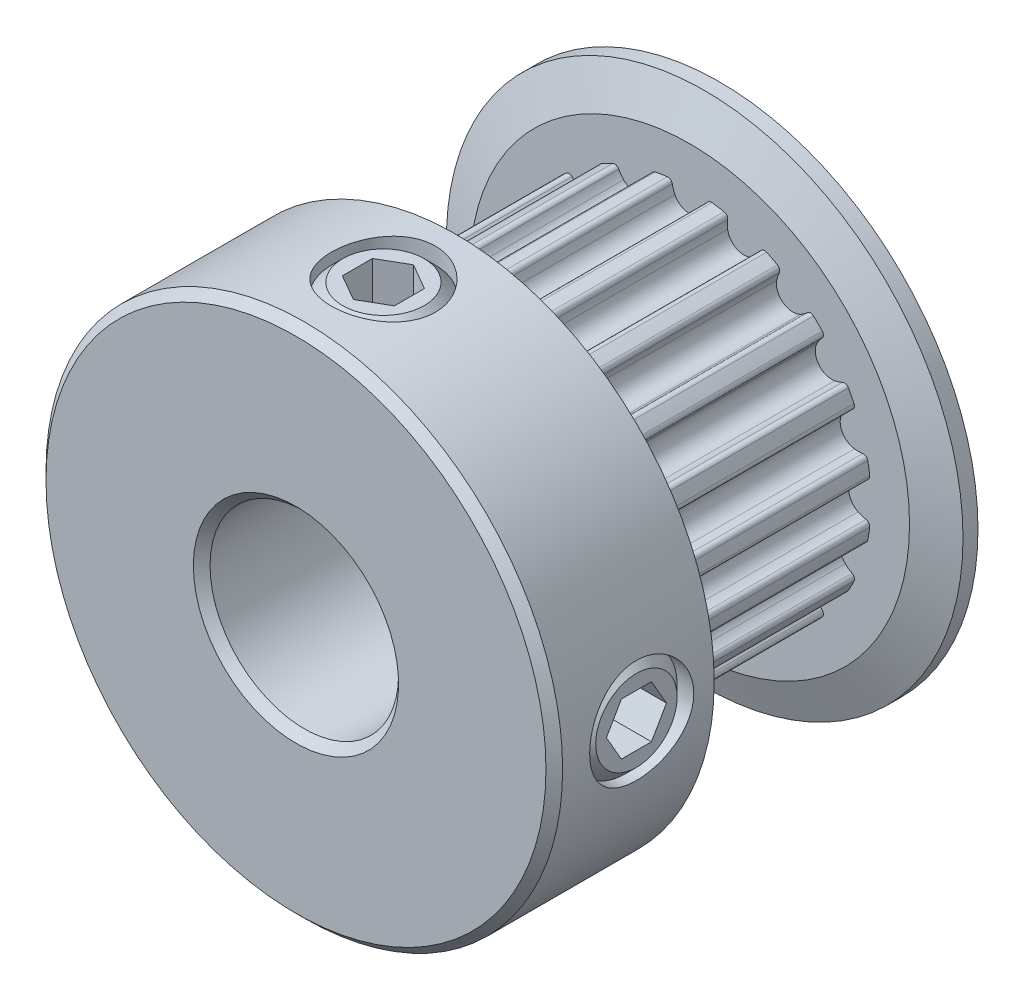
SolidWorks part; units mm, degrees
ref_plane "Front Plane" through (0, 0, 0) normal (0, 0, 1) x (1, 0, 0)
ref_plane "Top Plane" through (0, 0, 0) normal (0, 1, 0) x (1, 0, 0)
ref_plane "Right Plane" through (0, 0, 0) normal (1, 0, 0) x (0, 0, -1)
sketch "Sketch1" plane through (0, 0, 0) normal (0, 0, 1) x (1, 0, 0)
  line L1 (-1.7499, 5.3585) -> (1.7499, 5.3585) construction
  line L4 (0, 0) -> (0, 5.3585) construction
  line L5 (0, 5.3585) -> (0, 11.1847) construction
  line L6 (0, 6.3625) -> (1.9751, 6.0482) construction
  line L7 (1.9751, 6.0482) -> (2.6648, 5.8229) construction
  line L8 (1.9751, 6.0482) -> (1.7499, 5.3585) construction
  line L9 (-1.9751, 6.0482) -> (-1.7499, 5.3585) construction
  line L10 (-1.8963, 5.8067) -> (-2.841, 8.6995)
  line L11 (-2.841, 8.6995) -> (2.841, 8.6995)
  line L12 (2.841, 8.6995) -> (1.8963, 5.8067)
  circle A0 centre (0, 0) radius 6.3625 construction
  circle A1 centre (0, 0) radius 8.6995 construction
  circle A2 centre (0, 0) radius 6.1085 construction
  arc A3 (-0.4989, 5.6703) -> (0.4989, 5.6703) centre (0, 5.9135) ccw
  arc A4 (-0.4989, 5.6703) -> (-0.5855, 5.9387) centre (0.4, 6.1085) cw
  arc A5 (-1.8963, 5.8067) -> (-0.7518, 6.0621) centre (0, 0) cw
  arc A6 (-0.5855, 5.9387) -> (-0.7518, 6.0621) centre (-0.7333, 5.9132) ccw
  arc A7 (1.8963, 5.8067) -> (0.7518, 6.0621) centre (0, 0) ccw
  arc A8 (0.5855, 5.9387) -> (0.7518, 6.0621) centre (0.7333, 5.9132) cw
  arc A9 (0.4989, 5.6703) -> (0.5855, 5.9387) centre (-0.4, 6.1085) ccw
  point P6 (0, 20.9083)
  point P11 (0, 6.3625)
  point P13 (0, 8.6995)
  point P14 (0, 6.1085)
  dimension "D1" = 9.7237
  dimension "D2" = 4.8222
sketch "Sketch2" plane through (0, 0, 0) normal (1, 0, 0) x (0, 0, -1)
  line L0 (-7.135, 3.175) -> (7.135, 3.175)
  line L1 (-7.135, 3.175) -> (-7.135, 8.6995)
  line L2 (-1.75, 8.6995) -> (-7.135, 8.6995)
  line L3 (-2.255, 3.175) -> (-2.255, 8.6995) construction
  line L4 (-2.255, 8.6995) -> (-1.245, 8.6995) construction
  line L5 (-1.245, 8.6995) -> (-1.245, 6.1085) construction
  line L6 (-1.245, 6.1085) -> (6.125, 6.1085)
  line L7 (6.125, 6.1085) -> (6.125, 8.6995) construction
  line L8 (6.125, 8.6995) -> (7.135, 8.6995) construction
  line L9 (7.135, 8.6995) -> (7.135, 3.175)
  line L10 (-7.135, 0) -> (7.135, 0) construction
  line L11 (6.63, 8.6995) -> (6.125, 7.404)
  line L12 (-1.245, 7.404) -> (-1.75, 8.6995)
  line L14 (-1.245, 7.404) -> (-1.245, 6.1085)
  line L15 (6.125, 6.1085) -> (6.125, 7.404)
  line L16 (6.63, 8.6995) -> (7.135, 8.6995)
  arc A0 (-1.245, 7.404) -> (-1.75, 8.6995) centre (-3.1592, 7.404) ccw construction
  arc A1 (6.125, 7.404) -> (6.63, 8.6995) centre (8.0392, 7.404) cw construction
  point P12 (-1.245, 7.404)
  point P14 (-1.75, 8.6995)
  point P20 (6.125, 7.404)
  point P21 (6.63, 8.6995)
  point P25 (6.125, 0)
  point P26 (-1.245, 0)
  dimension "OA" = 14.27
  dimension "Bore" = 6.35
  dimension "Outside Width" = 8.38
  dimension "Inside Width" = 7.37
revolve "Revolve1" add sketch "Sketch2" angle 360 mid plane about L10
sketch "Sketch3" plane through (0, 0, 0) normal (0, 0, 1) x (1, 0, 0)
  line L6 (2.841, 8.6995) -> (-2.841, 8.6995)
  line L7 (1.8963, 5.8067) -> (2.841, 8.6995)
  line L8 (-2.841, 8.6995) -> (-1.8963, 5.8067)
  line L9 (2.841, 8.6995) -> (-2.841, 8.6995)
  line L10 (1.8963, 5.8067) -> (2.841, 8.6995)
  line L11 (-2.841, 8.6995) -> (-1.8963, 5.8067)
  arc A8 (1.8963, 5.8067) -> (0.7518, 6.0621) centre (0, 0) ccw
  arc A9 (0.7518, 6.0621) -> (0.5855, 5.9387) centre (0.7333, 5.9132) ccw
  arc A10 (0.4989, 5.6703) -> (0.5855, 5.9387) centre (-0.4, 6.1085) ccw
  arc A11 (-0.4989, 5.6703) -> (0.4989, 5.6703) centre (0, 5.9135) ccw
  arc A12 (-0.5855, 5.9387) -> (-0.4989, 5.6703) centre (0.4, 6.1085) ccw
  arc A13 (-0.5855, 5.9387) -> (-0.7518, 6.0621) centre (-0.7333, 5.9132) ccw
  arc A14 (-0.7518, 6.0621) -> (-1.8963, 5.8067) centre (0, 0) ccw
  arc A15 (1.8963, 5.8067) -> (0.7518, 6.0621) centre (0, 0) ccw
  arc A16 (0.7518, 6.0621) -> (0.5855, 5.9387) centre (0.7333, 5.9132) ccw
  arc A17 (0.4989, 5.6703) -> (0.5855, 5.9387) centre (-0.4, 6.1085) ccw
  arc A18 (-0.4989, 5.6703) -> (0.4989, 5.6703) centre (0, 5.9135) ccw
  arc A19 (-0.5855, 5.9387) -> (-0.4989, 5.6703) centre (0.4, 6.1085) ccw
  arc A20 (-0.5855, 5.9387) -> (-0.7518, 6.0621) centre (-0.7333, 5.9132) ccw
  arc A21 (-0.7518, 6.0621) -> (-1.8963, 5.8067) centre (0, 0) ccw
  dimension "D1" = 0
extrude "Cut-Extrude1" cut sketch "Sketch3" against normal up to vertex (6.125 mm away) from vertex up to point (0, 6.1085, -6.125) starting at point (0, 6.1085, 1.245)
pattern_circular "CirPattern1" count 20 over 360 about axis through (0, 0, 7.135) along (0, 0, 1) of "Cut-Extrude1"
sketch "Sketch4" plane through (0, 0, 0) normal (1, 0, 0) x (0, -1, 0)
  line L0 (0, -1.245) -> (0, -7.135) construction
  line L1 (-3.175, -7.135) -> (3.175, -7.135) construction
  line L2 (7.404, -1.245) -> (-7.404, -1.245) construction
  circle A0 centre (0, -4.19) radius 1.7526
extrude "Cut-Extrude2" cut sketch "Sketch4" along normal through all
ref_plane "Plane1" through (0, 0, 4.19) normal (0, 0, 1) x (1, 0, 0)
sketch "Sketch5" plane through (0, 0, 4.19) normal (0, 0, 1) x (1, 0, 0)
  line L0 (0, 0) -> (0, 8.6995) construction
  line L1 (3.175, -1.3716) -> (3.175, 0)
  line L2 (3.556, -1.7526) -> (8.1401, -1.7526)
  line L3 (3.175, 0) -> (8.6995, 0) construction
  line L4 (3.175, 0) -> (8.5211, 0)
  line L5 (8.5211, 0) -> (8.5211, -1.3716)
  line L6 (3.556, -1.7526) -> (3.175, -1.3716)
  line L7 (8.5211, -1.3716) -> (8.1401, -1.7526)
  circle A0 centre (0, 0) radius 8.6995 construction
  circle A1 centre (0, 0) radius 3.175 construction
  point P2 (3.175, -1.7526)
  point P11 (8.5211, -1.7526)
revolve "Revolve2" add sketch "Sketch5" angle 360 mid plane about L4
sketch "Sketch6" plane through (8.5211, 5.3841, 0) normal (-1, 0, 0) x (0, -1, 0)
  line L1 (5.3841, 5.2019) -> (4.5078, 4.6959)
  line L2 (4.5078, 4.6959) -> (4.5078, 3.6841)
  line L3 (4.5078, 3.6841) -> (5.3841, 3.1781)
  line L4 (5.3841, 3.1781) -> (6.2604, 3.6841)
  line L5 (6.2604, 3.6841) -> (6.2604, 4.6959)
  line L6 (6.2604, 4.6959) -> (5.3841, 5.2019)
  circle A0 centre (5.3841, 4.19) radius 0.8763 construction
  dimension "D1" = 1.7526
extrude "Cut-Extrude3" cut sketch "Sketch6" along normal blind 1.3144
pattern_circular "CirPattern3" count 2 over 90 about axis through (0, 0, 7.135) along (0, 0, 1) of "Cut-Extrude2", "Revolve2", "Cut-Extrude3"
chamfer "Chamfer1" distance 0.2807 angle 45 2 edges at (3.175, 0, 7.135) (8.6995, 0, 7.135)
ref_axis "Center Axis 1" through (0, 0, -7.135) along (0, 0, 1)
ref_plane "Contact Plane 1" through (0, 0, 7.135) normal (0, 0, 1) x (1, 0, 0)
ref_plane "Contact Plane 2" through (0, 0, -7.135) normal (0, 0, -1) x (-1, 0, 0)
equation "\"D2@Sketch1\"= \"D1@Sketch1\" / 2"
equation "\"D1@Sketch6\" = \"Set Screw@Sketch4\" / 2"
equation "\"D1@Cut-Extrude3\" = \"D1@Sketch6\"*.75"
